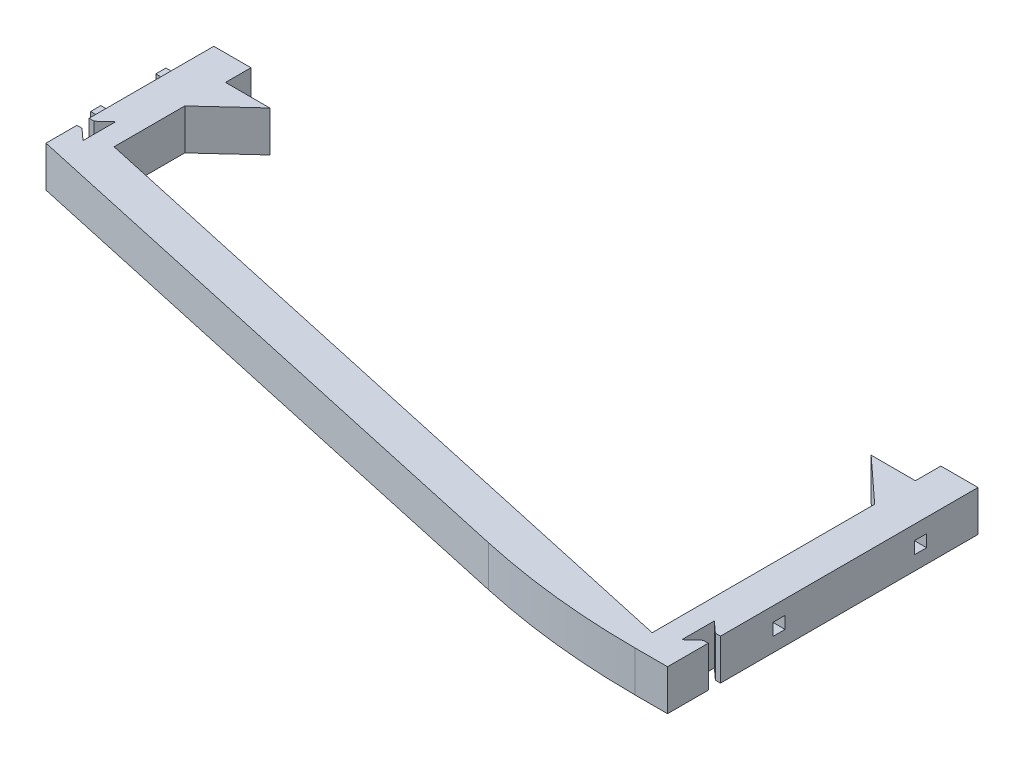
SolidWorks part; units mm, degrees
ref_plane "Přední rovina" through (0, 0, 0) normal (0, 0, 1) x (1, 0, 0)
ref_plane "Horní rovina" through (0, 0, 0) normal (0, 1, 0) x (1, 0, 0)
ref_plane "Pravá rovina" through (0, 0, 0) normal (1, 0, 0) x (0, 0, -1)
sketch "Skica1" plane through (0, 0, 0) normal (0, 1, 0) x (1, 0, 0)
  line L0 (0, 0) -> (0, -66)
  line L1 (0, -66) -> (-150.15, -32.9681)
  line L2 (-150.15, -32.9681) -> (-150.15, 0)
  line L3 (-150.15, 0) -> (-142.85, 0)
  line L4 (-142.85, 0) -> (-142.85, -26.8948)
  line L5 (-142.85, -26.8948) -> (-7.3, -56.7147)
  line L6 (-7.3, -56.7147) -> (-7.3, 0)
  line L7 (-7.3, 0) -> (0, 0)
  dimension "D1" = 66
  dimension "D2" = 7.3
  dimension "D3" = 7.3
  dimension "D4" = 150.15
  dimension "D5" = 7.5
  dimension "D6" = 77.593
extrude "Přidat vysunutím1" add sketch "Skica1" along normal blind 8
sketch "Skica3" plane through (0, 8, 0) normal (0, 1, 0) x (1, 0, 0)
  line L12 (0, -66) -> (0, 0) construction
  line L13 (-3.2, -48.6) -> (0, -48.6)
  line L14 (-3.2, -48.6) -> (-3.2, -55)
  line L15 (-3.2, -55) -> (0, -55)
  line L16 (0, -48.6) -> (0, -55)
  line L17 (0, -50.6) -> (-1, -50.6)
  line L18 (-1, -50.6) -> (-3.2, -48.6)
  line L19 (-3.2, -55) -> (-1, -53)
  line L20 (-1, -53) -> (0, -53)
  line L21 (0, -53) -> (0, -50.6)
  dimension "D1" = 6.4
  dimension "D2" = 3.2
  dimension "D3" = 2.4
  dimension "D4" = 2
  dimension "D5" = 1
  dimension "D6" = 1
  dimension "D7" = 11
extrude "Odebrat vysunutím1" cut sketch "Skica3" against normal through all contours L19 L20 L16 L17 L18 L14 region at (-1.9157, 8, 51.8)
sketch "Skica6" plane through (0, 8, 0) normal (0, 1, 0) x (1, 0, 0)
  line L0 (-150.15, 0) -> (-150.15, -32.9681) construction
  line L9 (-150.15, -5) -> (-134.15, -5)
  line L10 (-150.15, -5) -> (-150.15, -13)
  line L11 (-150.15, -13) -> (-134.15, -13)
  line L12 (-134.15, -5) -> (-134.15, -13)
  line L13 (-142.85, 0) -> (-150.15, 0) construction
  line L14 (0, -50.6) -> (0, 0) construction
  line L15 (0, -5) -> (-16, -5)
  line L16 (0, -5) -> (0, -13)
  line L17 (0, -13) -> (-16, -13)
  line L18 (-16, -5) -> (-16, -13)
  line L19 (0, 0) -> (-7.3, 0) construction
  dimension "D1" = 5
  dimension "D2" = 16
  dimension "D3" = 5
  dimension "D4" = 8
  dimension "D5" = 16
  dimension "D6" = 8
extrude "Přidat vysunutím3" add sketch "Skica6" against normal blind 8 contours L15 L18 L17 L16 | L9 L12 L11 L10
sketch "Skica9" plane through (0, 0, 0) normal (0, -1, 0) x (1, 0, 0)
  line L8 (-142.85, 13) -> (-134.15, 13)
  line L9 (-134.15, 13) -> (-134.15, 5)
  line L10 (-134.15, 5) -> (-142.85, 13)
  line L11 (-16, 13) -> (-7.3, 13)
  line L12 (-7.3, 13) -> (-16, 5)
  line L13 (-16, 5) -> (-16, 13)
extrude "Odebrat vysunutím4" cut sketch "Skica9" against normal through all
sketch "Skica4" plane through (0, 0, 0) normal (1, 0, 0) x (0, 0, -1)
  line L26 (-40.3, 5.2) -> (-37.9, 5.2)
  line L27 (-40.3, 5.2) -> (-40.3, 2.8)
  line L28 (-40.3, 2.8) -> (-37.9, 2.8)
  line L29 (-37.9, 5.2) -> (-37.9, 2.8)
  line L30 (-12.5, 5.2) -> (-10.1, 5.2)
  line L31 (-12.5, 5.2) -> (-12.5, 2.8)
  line L32 (-12.5, 2.8) -> (-10.1, 2.8)
  line L33 (-10.1, 5.2) -> (-10.1, 2.8)
  line L34 (-50.6, 8) -> (0, 8) construction
  line L35 (-66, 0) -> (-53, 0) construction
  line L37 (0, 8) -> (0, 0) construction
  point P18 (-11.3, 2.8)
  dimension "D4" = 10.1
  dimension "D10" = 2.4
  dimension "D11" = 2.4
  dimension "D12" = 2.8
  dimension "D13" = 2.8
  dimension "D14" = 2.4
  dimension "D15" = 2.4
  dimension "D16" = 25.4
extrude "Odebrat vysunutím2" cut sketch "Skica4" against normal blind 4.4
sketch "Skica5" plane through (-150.15, 0, 0) normal (-1, 0, 0) x (0, 0, 1)
  line L0 (0, 8) -> (32.9681, 8) construction
  line L1 (5.4, 5) -> (7.4, 5)
  line L2 (5.4, 5) -> (5.4, 3)
  line L3 (5.4, 3) -> (7.4, 3)
  line L4 (7.4, 5) -> (7.4, 3)
  line L5 (18.2, 5) -> (20.2, 5)
  line L6 (18.2, 5) -> (18.2, 3)
  line L7 (18.2, 3) -> (20.2, 3)
  line L8 (20.2, 5) -> (20.2, 3)
  line L9 (0, 8) -> (0, 0) construction
  dimension "D1" = 2
  dimension "D2" = 2
  dimension "D3" = 3
  dimension "D4" = 5.4
  dimension "D5" = 10.8
  dimension "D6" = 2
  dimension "D7" = 2
  dimension "D8" = 3
extrude "Přidat vysunutím2" add sketch "Skica5" along normal blind 4
sketch "Skica10" plane through (0, 8, 0) normal (0, 1, 0) x (1, 0, 0)
  line L0 (-150.15, -26.9) -> (-149.15, -26.9)
  line L5 (-142.85, 0) -> (-150.15, 0) construction
  line L6 (-150.15, 0) -> (-150.15, -32.9681) construction
  line L7 (-150.15, -24.5) -> (-149.15, -24.5)
  line L8 (-149.15, -24.5) -> (-146.95, -22.5)
  line L9 (-146.95, -22.5) -> (-146.95, -28.9)
  line L10 (-146.95, -28.9) -> (-149.15, -26.9)
  line L11 (-150.15, -26.9) -> (-150.15, -24.5)
  dimension "D1" = 6.4
  dimension "D2" = 2.4
  dimension "D3" = 1
  dimension "D4" = 1
  dimension "D5" = 2
  dimension "D6" = 3.2
  dimension "D7" = 22.5
extrude "Odebrat vysunutím5" cut sketch "Skica10" against normal through all
sketch "Skica11" plane through (0, 8, 0) normal (0, 1, 0) x (1, 0, 0)
  line L0 (0, -61) -> (-22.7281, -61)
  line L1 (0, -66) -> (0, -53) construction
  line L2 (-150.15, -32.9681) -> (0, -66) construction
  line L3 (-22.7281, -61) -> (0, -66)
  line L4 (0, -66) -> (0, -61)
  dimension "D1" = 5
extrude "Odebrat vysunutím6" cut sketch "Skica11" against normal through all
fillet "Zaoblit1" radius 150 1 edges at (-22.7281, 4, 61)
